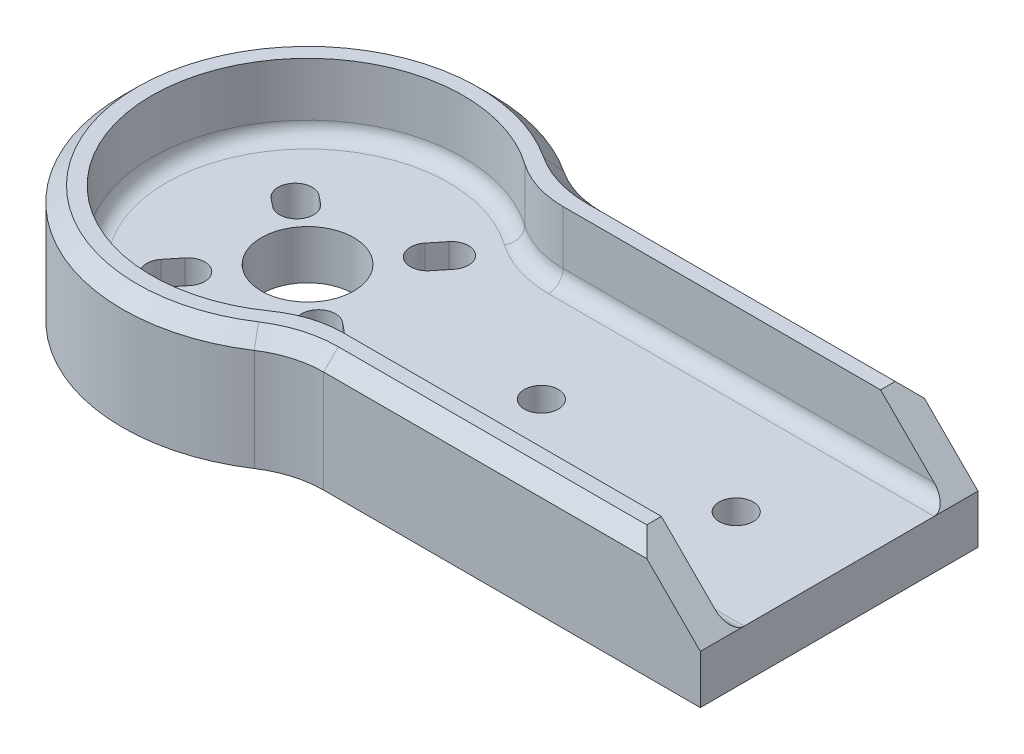
SolidWorks part; units mm, degrees
ref_plane "Front Plane" through (0, 0, 0) normal (0, 0, 1) x (1, 0, 0)
ref_plane "Top Plane" through (0, 0, 0) normal (0, 1, 0) x (1, 0, 0)
ref_plane "Right Plane" through (0, 0, 0) normal (1, 0, 0) x (0, 0, -1)
sketch "Sketch1" plane through (0, 0, 0) normal (0, 1, 0) x (1, 0, 0)
  line L1 (12.5673, 14.25) -> (54.5673, 14.25)
  line L3 (12.5673, -14.25) -> (54.5673, -14.25)
  line L4 (54.5673, 14.25) -> (54.5673, -14.25)
  arc A0 (12.5673, 14.25) -> (12.5673, -14.25) centre (0, 0) ccw
  dimension "D1" = 38
  dimension "D2" = 42
extrude "Boss-Extrude1" add sketch "Sketch1" along normal blind 5
sketch "Sketch2" plane through (0, 5, 0) normal (0, 1, 0) x (1, 0, 0)
  circle A0 centre (0, 0) radius 4.75
  dimension "D1" = 9.5
extrude "Cut-Extrude1" cut sketch "Sketch2" against normal blind 5
sketch "Sketch4" plane through (0, 5, 0) normal (0, 1, 0) x (1, 0, 0)
  circle A0 centre (24, 0) radius 1.75
  circle A1 centre (44, 0) radius 1.75
  circle A2 centre (0, 0) radius 4.75 construction
  dimension "D1" = 3.5
  dimension "D2" = 3.5
  dimension "D3" = 24
  dimension "D4" = 20
extrude "Cut-Extrude3" cut sketch "Sketch4" against normal blind 5
sketch "Sketch5" plane through (0, 5, 0) normal (0, 1, 0) x (1, 0, 0)
  line L1 (54.5673, 14.25) -> (12.5673, 14.25)
  line L2 (54.5673, 14.25) -> (54.5673, 11.25)
  line L3 (54.5673, 11.25) -> (11.3771, 11.25)
  line L5 (54.5673, -14.25) -> (12.5673, -14.25)
  line L6 (54.5673, -14.25) -> (54.5673, -11.25)
  line L7 (54.5673, -11.25) -> (11.3771, -11.25)
  arc A0 (12.5673, 14.25) -> (12.5673, -14.25) centre (0, 0) ccw
  arc A1 (11.3771, 11.25) -> (11.3771, -11.25) centre (0, 0) ccw
  arc A2 (12.5673, 14.25) -> (12.5673, -14.25) centre (0, 0) ccw construction
  dimension "D1" = 3
  dimension "D3" = 3
  dimension "D4" = 0
  dimension "D2" = 3
extrude "Boss-Extrude2" add sketch "Sketch5" along normal blind 7
fillet "Fillet1" radius 10 2 edges at (12.5673, 6, -14.25) (12.5673, 6, 14.25)
fillet "Fillet2" radius 10 2 edges at (11.3771, 8.5, -11.25) (11.3771, 8.5, 11.25)
fillet "Fillet3" radius 1.5 5 edges at (34.7743, 5, 11.25) (11.9589, 5, 11.7177) (34.7743, 5, -11.25) (11.9589, 5, -11.7177) (-16, 5, 0)
chamfer "Chamfer1" distance 7 angle 45 2 edges at (54.5673, 12, 12.75) (54.5673, 12, -12.75)
chamfer "Chamfer2" distance 1.5 angle 45 5 edges at (31.7357, 12, -14.25) (31.7357, 12, 14.25) (13.0423, 12, -14.6682) (13.0423, 12, 14.6682) (-19, 12, 0)
sketch "Sketch6" plane through (0, 5, 0) normal (0, 1, 0) x (1, 0, 0)
  line L0 (6.5943, 8.171) -> (0, 0) construction
  line L1 (6.8571, 5.7102) -> (7.9561, 7.072)
  line L2 (4.1334, 7.9082) -> (5.2324, 9.2701)
  line L3 (-6.8571, -5.7102) -> (-7.9561, -7.072)
  line L4 (-4.1334, -7.9082) -> (-5.2324, -9.2701)
  line L5 (0, 0) -> (9.425, -7.6062) construction
  line L6 (6.9355, -3.3483) -> (7.7137, -3.9764)
  line L7 (4.7374, -6.072) -> (5.5156, -6.7)
  line L8 (-6.9355, 3.3483) -> (-7.7137, 3.9764)
  line L9 (-4.7374, 6.072) -> (-5.5156, 6.7)
  arc A0 (7.9561, 7.072) -> (5.2324, 9.2701) centre (6.5943, 8.171) ccw
  arc A1 (4.1334, 7.9082) -> (6.8571, 5.7102) centre (5.4952, 6.8092) ccw
  arc A2 (-4.1334, -7.9082) -> (-6.8571, -5.7102) centre (-5.4952, -6.8092) ccw
  arc A3 (-7.9561, -7.072) -> (-5.2324, -9.2701) centre (-6.5943, -8.171) ccw
  arc A4 (5.5156, -6.7) -> (7.7137, -3.9764) centre (6.6146, -5.3382) ccw
  arc A5 (6.9355, -3.3483) -> (4.7374, -6.072) centre (5.8365, -4.7102) ccw
  arc A6 (-6.9355, 3.3483) -> (-4.7374, 6.072) centre (-5.8365, 4.7102) ccw
  arc A7 (-5.5156, 6.7) -> (-7.7137, 3.9764) centre (-6.6146, 5.3382) ccw
  point P16 (0, 0)
  point P31 (0, 0)
  dimension "D1" = 3.5
  dimension "D2" = 10.5
  dimension "D4" = 3.5
  dimension "D8" = 3.5
  dimension "D9" = 8.5
  dimension "D10" = 1
  dimension "D11" = 3.5
  dimension "D3" = 0
  dimension "D5" = 1.75
  dimension "D6" = 1.75
  dimension "D12" = 1.75
  dimension "D13" = 1.75
  dimension "D7" = 2
  dimension "D14" = 2
extrude "Cut-Extrude4" cut sketch "Sketch6" against normal blind 10
